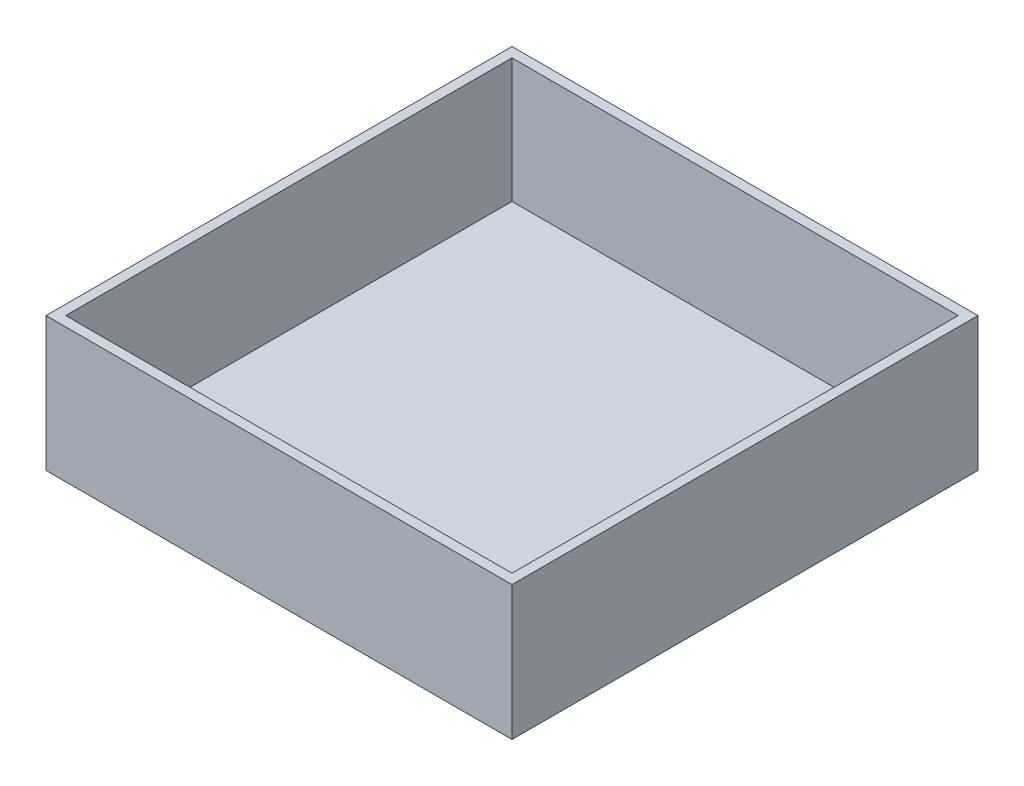
SolidWorks part; units mm, degrees
ref_plane "Front Plane" through (0, 0, 0) normal (0, 0, 1) x (1, 0, 0)
ref_plane "Top Plane" through (0, 0, 0) normal (0, 1, 0) x (1, 0, 0)
ref_plane "Right Plane" through (0, 0, 0) normal (1, 0, 0) x (0, 0, -1)
sketch "Sketch1" plane through (0, 0, 0) normal (0, 1, 0) x (1, 0, 0)
  line L0 (-143.65, -143.65) -> (-143.65, 143.65)
  line L1 (150, -150) -> (-150, -150)
  line L2 (150, -150) -> (150, 150)
  line L3 (150, 150) -> (-150, 150)
  line L4 (-150, -150) -> (-150, 150)
  line L5 (150, -150) -> (-150, 150) construction
  line L6 (150, 150) -> (-150, -150) construction
  line L7 (143.65, 143.65) -> (-143.65, 143.65)
  line L8 (143.65, -143.65) -> (143.65, 143.65)
  line L9 (143.65, -143.65) -> (-143.65, -143.65)
  point P0 (0, 0)
  point P10 (0, 0)
  dimension "D1" = 300
  dimension "D2" = 6.35
extrude "Boss-Extrude1" add sketch "Sketch1" along normal blind 80
sketch "Sketch2" plane through (0, 0, 0) normal (0, -1, 0) x (1, 0, 0)
  line L0 (150, -150) -> (-150, -150) construction
  line L1 (150, 150) -> (150, -150) construction
  line L2 (-150, 150) -> (150, 150) construction
  line L3 (-150, -150) -> (-150, 150) construction
  line L4 (150, -150) -> (-150, -150)
  line L5 (150, 150) -> (150, -150)
  line L6 (-150, 150) -> (150, 150)
  line L7 (-150, -150) -> (-150, 150)
extrude "Boss-Extrude2" add sketch "Sketch2" along normal blind 6.35
